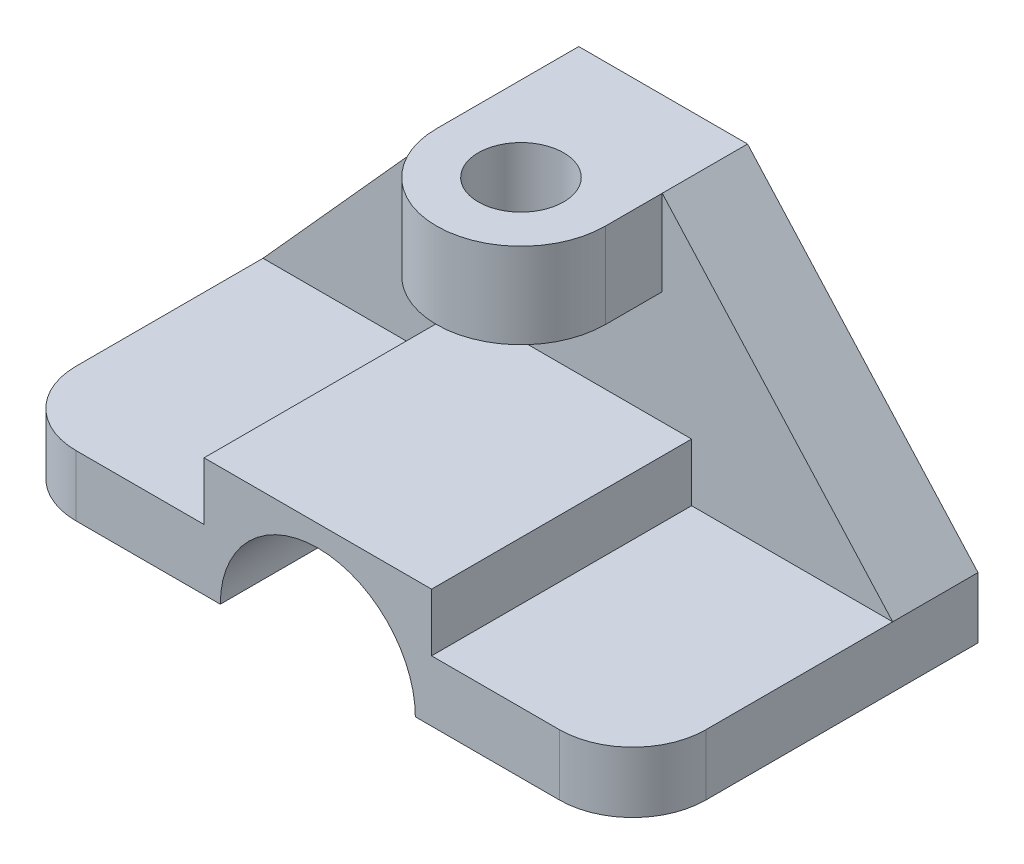
SolidWorks part; units mm, degrees
ref_plane "정면" through (0, 0, 0) normal (0, 0, 1) x (1, 0, 0)
ref_plane "윗면" through (0, 0, 0) normal (0, 1, 0) x (1, 0, 0)
ref_plane "우측면" through (0, 0, 0) normal (1, 0, 0) x (0, 0, -1)
sketch "스케치1" plane through (0, 0, 0) normal (0, 0, 1) x (1, 0, 0)
  line L0 (0, 0) -> (0, 74.9563) construction
  line L1 (-77.5, 0) -> (-24, 0)
  line L2 (77.5, 0) -> (77.5, 15)
  line L3 (-77.5, 0) -> (-77.5, 15)
  line L4 (77.5, 15) -> (28, 15)
  line L5 (-77.5, 15) -> (-28, 15)
  line L6 (28, 15) -> (28, 29.2185)
  line L7 (-28, 15) -> (-28, 29.2185)
  line L8 (28, 29.2185) -> (-28, 29.2185)
  line L9 (-77.5, 15) -> (-20.7745, 78)
  line L10 (77.5, 15) -> (20.7745, 78)
  line L11 (24, 0) -> (77.5, 0)
  line L12 (-20.7745, 78) -> (-20.7745, 57)
  line L13 (20.7745, 78) -> (20.7745, 57)
  line L14 (-20.7745, 57) -> (20.7745, 57)
  arc A0 (24, 0) -> (-24, 0) centre (0, 0) ccw
  point P11 (0, 29.2185)
  point P18 (0, 57)
  dimension "D1" = 155
  dimension "D2" = 15
  dimension "D3" = 48
  dimension "D4" = 63
  dimension "D5" = 56
extrude "보스-돌출1" add sketch "스케치1" along normal blind 85 contours A0 L0 L8 L7 L5 L3 L1 | L0 A0 L11 L2 L4 L6 L8 region at (-41.519, 11.6518, 0) region at (41.519, 11.6518, 0)
extrude "보스-돌출2" add sketch "스케치1<3>" along normal blind 21 contours L8 L0 L14 L12 L9 L5 L7 | L0 L8 L6 L4 L10 L13 L14 region at (-32.9007, 38.4456, 0) region at (32.9007, 38.4456, 0)
sketch "스케치1<3>" plane through (0, 0, 0) normal (0, 0, 1) x (1, 0, 0) same geometry as "스케치1"
sketch "스케치2" plane through (0, 15, 0) normal (0, 1, 0) x (1, 0, 0)
  line L0 (-77.5, -85) -> (-77.5, -21) construction
  line L1 (-77.5, -85) -> (-28, -85) construction
  circle A0 centre (-59.5, -67) radius 18
  line M3 (-77.5, -21) -> (-77.5, -85)
  line M4 (-77.5, -85) -> (-28, -85)
sketch "스케치3" plane through (0, 15, 0) normal (0, 1, 0) x (1, 0, 0)
  line L0 (77.5, -85) -> (77.5, -21) construction
  line L1 (77.5, -85) -> (28, -85) construction
  line L2 (-77.5, -67) -> (-77.5, -85)
  line L3 (-77.5, -85) -> (-77.5, -21) construction
  line L4 (-77.5, -85) -> (-59.5, -85)
  line L5 (-77.5, -85) -> (-28, -85) construction
  line L6 (59.5, -85) -> (77.5, -85)
  line L7 (77.5, -85) -> (77.5, -67)
  circle A0 centre (59.5, -67) radius 18
  circle A1 centre (-59.5, -67) radius 18 construction
  line M2 (77.5, -85) -> (77.5, -21)
  line M5 (28, -85) -> (77.5, -85)
extrude "컷-돌출1" cut sketch "스케치3" against normal blind 21 contours A0 M5 M2 region at (73.4794, 15, 80.9794)
extrude "컷-돌출2" cut sketch "스케치2" against normal blind 21 contours A0 M3 M4 region at (-73.4794, 15, 80.9794)
sketch "스케치4" plane through (0, 57, 0) normal (0, 1, 0) x (1, 0, 0)
  line L0 (-20.7745, 0) -> (-20.7745, -35)
  line L1 (-20.7745, -35) -> (20.7745, -35)
  line L2 (20.7745, -35) -> (20.7745, 0)
  line L3 (20.7745, 0) -> (-20.7745, 0)
  dimension "D1" = 35
extrude "보스-돌출3" add sketch "스케치4" along normal blind 21
sketch "스케치5" plane through (0, 78, 0) normal (0, 1, 0) x (1, 0, 0)
  line L0 (-20.7745, -35) -> (20.7745, -35) construction
  line L1 (-20.7745, -21) -> (-20.7745, -35) construction
  line L2 (20.7745, -35) -> (20.7745, -21) construction
  circle A0 centre (0, -35) radius 20.7745
  circle A1 centre (0, -35) radius 10.5
  line M6 (-20.7745, -35) -> (20.7745, -35)
extrude "보스-돌출4" add sketch "스케치5" against normal blind 21 contours A1 A0 M6 | A1 A0 M6 region at (15.6373, 78, 34.5355) region at (0, 78, 55.31)
sketch "스케치7" plane through (0, 78, 0) normal (0, 1, 0) x (1, 0, 0)
  line L0 (-10.5, -35) -> (10.5, -35) construction
  circle A0 centre (0, -35) radius 10.5
extrude "컷-돌출3" cut sketch "스케치7" against normal blind 21
